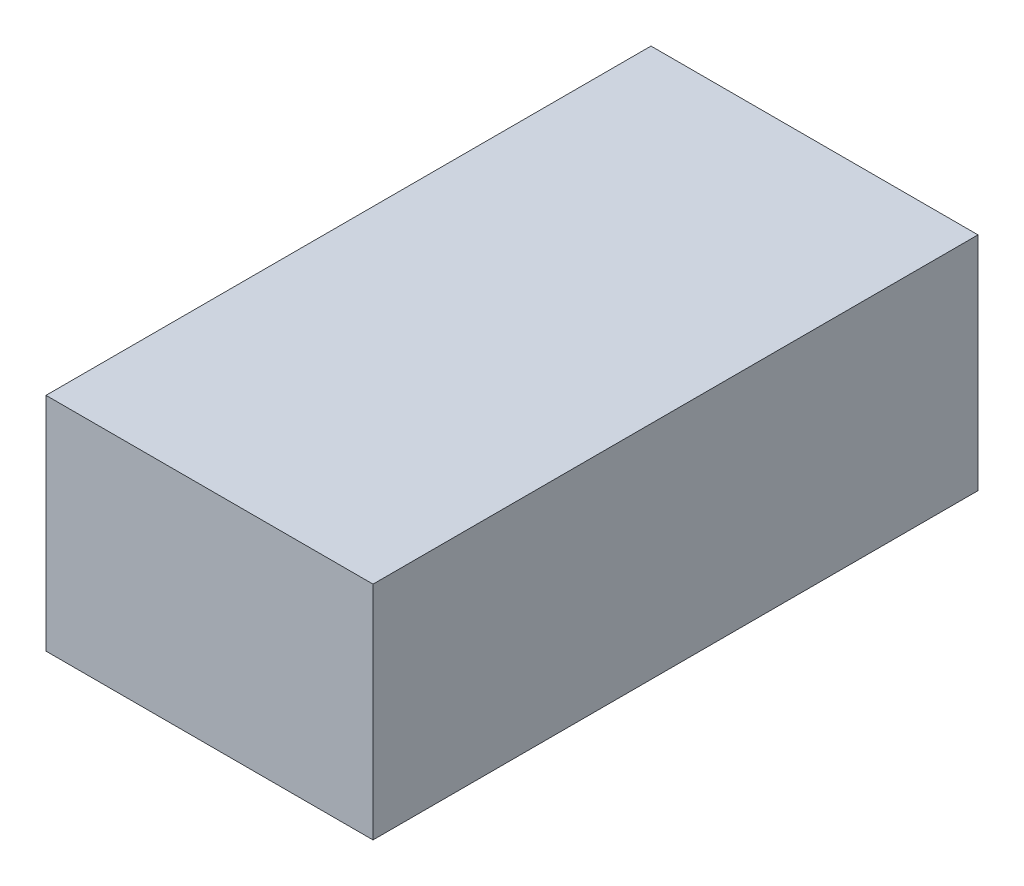
SolidWorks part; units mm, degrees
other "fluid_domain"
ref_plane "Front Plane" through (0, 0, 0) normal (0, 0, 1) x (1, 0, 0)
ref_plane "Top Plane" through (0, 0, 0) normal (0, 1, 0) x (1, 0, 0)
ref_plane "Right Plane" through (0, 0, 0) normal (1, 0, 0) x (0, 0, -1)
other "Configuration Table"
sketch "Sketch1" plane through (0, 0, 0) normal (1, 0, 0) x (0, 0, -1)
  line L1 (2500, -355) -> (-1200, -355)
  line L2 (2500, -355) -> (2500, 1000)
  line L3 (2500, 1000) -> (-1200, 1000)
  line L4 (-1200, -355) -> (-1200, 1000)
  line L5 (2500, -355) -> (-1200, 1000) construction
  line L6 (2500, 1000) -> (-1200, -355) construction
extrude "air_box" add sketch "Sketch1" along normal blind 2000 from offset 800 separate body offset against normal yes
sketch "Sketch2" plane through (0, 0, 0) normal (1, 0, 0) x (0, 0, -1)
  circle A0 centre (0, 0) radius 360
  circle A1 centre (0, 0) radius 200
extrude "wheel" add sketch "Sketch2" along normal blind 285 from offset 190 separate body offset against normal yes
sketch "Sketch3" plane through (0, 0, 0) normal (1, 0, 0) x (0, 0, -1)
  circle A0 centre (0, 0) radius 360
extrude "cover" add sketch "Sketch3" along normal blind 10 from offset 200 separate body offset against normal yes
sketch "Sketch4" plane through (0, 0, 0) normal (1, 0, 0) x (0, 0, -1)
  circle A0 centre (0, 0) radius 164
extrude "rotor" add sketch "Sketch4" along normal mid plane 32 separate body
sketch "Sketch5" plane through (0, 0, 0) normal (1, 0, 0) x (0, 0, -1)
  line L1 (32, 88) -> (-32, 88)
  line L2 (32, 88) -> (32, 192)
  line L3 (32, 192) -> (-32, 192)
  line L4 (-32, 88) -> (-32, 192)
  line L5 (32, 88) -> (-32, 192) construction
  line L6 (32, 192) -> (-32, 88) construction
extrude "throat_outer" add sketch "Sketch5" along normal blind 82 from offset 18 separate body
sketch "Sketch6" plane through (0, 0, 0) normal (1, 0, 0) x (0, 0, -1)
  line L1 (32, 88) -> (-300, 88)
  line L2 (32, 88) -> (32, 192)
  line L3 (32, 192) -> (-300, 192)
  line L4 (-300, 88) -> (-300, 192)
  line L5 (32, 88) -> (-300, 192) construction
  line L6 (32, 192) -> (-300, 88) construction
extrude "scoop_outer" add sketch "Sketch6" along normal blind 64 from offset 98 separate body
combine bodies "Combine1" operation type add bodies to combine 107 106
sketch "Sketch7" plane through (0, 0, 0) normal (1, 0, 0) x (0, 0, -1)
  line L1 (30, 90) -> (-30, 90)
  line L2 (30, 90) -> (30, 190)
  line L3 (30, 190) -> (-30, 190)
  line L4 (-30, 90) -> (-30, 190)
  line L5 (30, 90) -> (-30, 190) construction
  line L6 (30, 190) -> (-30, 90) construction
extrude "throat_inner" add sketch "Sketch7" along normal blind 91 from offset 10 separate body
sketch "Sketch8" plane through (0, 0, 0) normal (1, 0, 0) x (0, 0, -1)
  line L1 (30, 90) -> (-310, 90)
  line L2 (30, 90) -> (30, 190)
  line L3 (30, 190) -> (-310, 190)
  line L4 (-310, 90) -> (-310, 190)
  line L5 (30, 90) -> (-310, 190) construction
  line L6 (30, 190) -> (-310, 90) construction
extrude "scoop_inner" add sketch "Sketch8" along normal blind 60 from offset 100 separate body
combine bodies "Combine2" operation type subtract main body 108 bodies to subtract 109 110
sketch "Sketch9" plane through (0, 0, 0) normal (1, 0, 0) x (0, 0, -1)
  line L1 (28, 101) -> (-28, 101)
  line L2 (28, 101) -> (28, 119)
  line L3 (28, 119) -> (-28, 119)
  line L4 (-28, 101) -> (-28, 119)
  line L5 (28, 101) -> (-28, 119) construction
  line L6 (28, 119) -> (-28, 101) construction
extrude "louver1" add sketch "Sketch9" along normal blind 2 from offset 57 separate body
sketch "Sketch10" plane through (0, 0, 0) normal (1, 0, 0) x (0, 0, -1)
  line L1 (28, 121) -> (-28, 121)
  line L2 (28, 121) -> (28, 139)
  line L3 (28, 139) -> (-28, 139)
  line L4 (-28, 121) -> (-28, 139)
  line L5 (28, 121) -> (-28, 139) construction
  line L6 (28, 139) -> (-28, 121) construction
extrude "louver2" add sketch "Sketch10" along normal blind 2 from offset 57 separate body
sketch "Sketch11" plane through (0, 0, 0) normal (1, 0, 0) x (0, 0, -1)
  line L1 (28, 141) -> (-28, 141)
  line L2 (28, 141) -> (28, 159)
  line L3 (28, 159) -> (-28, 159)
  line L4 (-28, 141) -> (-28, 159)
  line L5 (28, 141) -> (-28, 159) construction
  line L6 (28, 159) -> (-28, 141) construction
extrude "louver3" add sketch "Sketch11" along normal blind 2 from offset 57 separate body
sketch "Sketch12" plane through (0, 0, 0) normal (1, 0, 0) x (0, 0, -1)
  line L1 (28, 161) -> (-28, 161)
  line L2 (28, 161) -> (28, 179)
  line L3 (28, 179) -> (-28, 179)
  line L4 (-28, 161) -> (-28, 179)
  line L5 (28, 161) -> (-28, 179) construction
  line L6 (28, 179) -> (-28, 161) construction
extrude "louver4" add sketch "Sketch12" along normal blind 2 from offset 57 separate body
combine bodies "Combine3" operation type subtract main body 102 bodies to subtract 103
combine bodies "Combine4" operation type subtract main body 116 bodies to subtract 104
combine bodies "Combine5" operation type subtract main body 117 bodies to subtract 105
combine bodies "Combine6" operation type subtract main body 118 bodies to subtract 111
combine bodies "Combine7" operation type subtract main body 119 bodies to subtract 112
combine bodies "Combine8" operation type subtract main body 120 bodies to subtract 113
combine bodies "Combine9" operation type subtract main body 121 bodies to subtract 114
combine bodies "Combine10" operation type subtract main body 122 bodies to subtract 115
